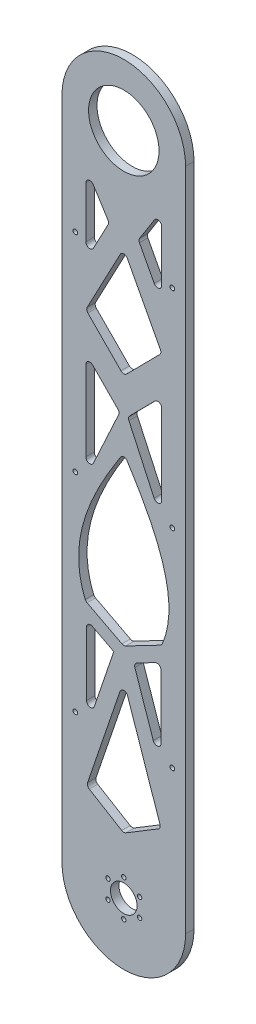
SolidWorks part; units mm, degrees
material "1060 Alloy"
ref_plane "Front Plane" through (0, 0, 0) normal (0, 0, 1) x (1, 0, 0)
ref_plane "Top Plane" through (0, 0, 0) normal (0, 1, 0) x (1, 0, 0)
ref_plane "Right Plane" through (0, 0, 0) normal (1, 0, 0) x (0, 0, -1)
sketch "Sketch2" plane through (0, 0, 0) normal (0, 0, 1) x (1, 0, 0)
  line L0 (0, 0) -> (0, 500) construction
  line L1 (-46.5, 0) -> (-46.5, 500)
  line L2 (46.5, 0) -> (46.5, 500)
  arc A0 (-46.5, 0) -> (46.5, 0) centre (0, 0) ccw
  arc A1 (46.5, 500) -> (-46.5, 500) centre (0, 500) ccw
  circle A2 centre (0, 500) radius 37.25 construction
  circle A3 centre (0, 0) radius 10
  circle A4 centre (0, 13.75) radius 1.65
  circle A5 centre (0, 0) radius 13.75 construction
  circle A6 centre (11.9078, 6.875) radius 1.65
  circle A7 centre (11.9078, -6.875) radius 1.65
  circle A8 centre (0, -13.75) radius 1.65
  circle A9 centre (-11.9078, -6.875) radius 1.65
  circle A10 centre (-11.9078, 6.875) radius 1.65
  point P3 (0, 250)
  point P27 (0, 0)
  dimension "D2" = 74.5
  dimension "D4" = 20
  dimension "D5" = 3.3
  dimension "D6" = 27.5
  dimension "D3" = 46.5
  dimension "D1" = 500
  dimension "D7" = 6
extrude "Boss-Extrude1" add sketch "Sketch2" along normal blind 6.35
sketch "Sketch4" plane through (0, 0, 6.35) normal (0, 0, 1) x (1, 0, 0)
  line L0 (0, 500) -> (0, 999.1647) construction
  line L29 (46.5, 500) -> (-46.5, 500) construction
  line L31 (28.0053, 59.376) -> (0, 42.4117)
  line L32 (0, 141.6934) -> (28.0053, 59.376)
  line L33 (-28.0053, 59.376) -> (0, 141.6934)
  line L34 (0, 42.4117) -> (-28.0053, 59.376)
  line L35 (-7.5, 156.9059) -> (-28.0053, 96.6336)
  line L36 (-28.0053, 167.5829) -> (-7.5, 156.9059)
  line L37 (-28.0053, 96.6336) -> (-28.0053, 167.5829)
  line L38 (28.0053, 167.5829) -> (7.5, 156.9059)
  line L39 (28.0053, 96.6336) -> (28.0053, 167.5829)
  line L40 (7.5, 156.9059) -> (28.0053, 96.6336)
  line L41 (0, 164.2751) -> (28.5505, 179.1412)
  line L42 (0, 164.2751) -> (-28.5505, 179.1412)
  line L43 (28.5505, 259.5868) -> (3, 314.9383)
  line L44 (28.5505, 340.7931) -> (28.5505, 259.5868)
  line L45 (3, 314.9383) -> (28.5505, 340.7931)
  line L46 (-3, 314.9383) -> (-28.5505, 340.7931)
  line L47 (-28.5505, 259.5868) -> (-3, 314.9383)
  line L48 (-28.5505, 340.7931) -> (-28.5505, 259.5868)
  line L49 (0, 423.1428) -> (-28.5505, 369.2462)
  line L50 (-28.5505, 369.2462) -> (0, 340.3557)
  line L51 (0, 340.3557) -> (28.5505, 369.2462)
  line L52 (0, 423.1428) -> (28.5505, 369.2462)
  line L53 (-28.5505, 462.0952) -> (-28.5505, 401.2902)
  line L54 (-11, 434.4215) -> (-28.5505, 462.0952)
  line L55 (-28.5505, 401.2902) -> (-11, 434.4215)
  line L56 (28.5505, 401.2902) -> (11, 434.4215)
  line L57 (28.5505, 462.0952) -> (28.5505, 401.2902)
  line L58 (11, 434.4215) -> (28.5505, 462.0952)
  arc A0 (46.5, 500) -> (-46.5, 500) centre (0, 500) ccw construction
  arc A1 (46.5, 500) -> (-46.5, 500) centre (0, 500) ccw construction
  spline S2 degree 3 poles (28.5505, 179.1412) (45.3203, 216.9857) (19.4301, 259.7903) (0, 290.0258) knots 0 0 0 0 1 1 1 1
  spline S3 degree 3 poles (-28.5505, 179.1412) (-45.3203, 216.9857) (-19.4301, 259.7903) (0, 290.0258) knots 0 0 0 0 1 1 1 1
extrude "Cut-Extrude1" cut sketch "Sketch4" against normal blind 10
fillet "Fillet3" radius 3 29 edges at (-11, 434.4215, 3.175) (-28.5505, 401.2902, 3.175) (28.5505, 401.2902, 3.175) (11, 434.4215, 3.175) (28.5505, 462.0952, 3.175) (-28.5505, 462.0952, 3.175) (0, 423.1428, 3.175) (-28.5505, 369.2462, 3.175) (28.5505, 369.2462, 3.175) (0, 340.3557, 3.175) (28.5505, 340.7931, 3.175) (-28.5505, 340.7931, 3.175) (-3, 314.9383, 3.175) (3, 314.9383, 3.175) (28.5505, 259.5868, 3.175) (-28.5505, 259.5868, 3.175) (28.5505, 179.1412, 3.175) (0, 290.0258, 3.175) (-28.5505, 179.1412, 3.175) (0, 164.2751, 3.175) (-28.0053, 96.6336, 3.175) (28.0053, 96.6336, 3.175) (7.5, 156.9059, 3.175) (-28.0053, 167.5829, 3.175) (28.0053, 167.5829, 3.175) (0, 141.6934, 3.175) (28.0053, 59.376, 3.175) (-28.0053, 59.376, 3.175) (0, 42.4117, 3.175)
sketch "Sketch5" plane through (0, 0, 6.35) normal (0, 0, 1) x (1, 0, 0)
  line L0 (0, -46.5) -> (108.8395, -46.5) construction
  line L1 (46.5, 100) -> (-46.5, 100) construction
  line L2 (46.5, 0) -> (46.5, 500) construction
  line L3 (-46.5, 500) -> (-46.5, 0) construction
  line L4 (-46.5, 106.35) -> (46.5, 106.35) construction
  line L5 (36.5, 106.35) -> (36.5, 100) construction
  line L6 (0, 106.35) -> (0, 100) construction
  line L7 (-46.5, 256.35) -> (46.5, 256.35) construction
  line L8 (-46.5, 181.35) -> (46.5, 181.35) construction
  line L9 (-46.5, 337.7) -> (46.5, 337.7) construction
  arc A1 (-46.5, 0) -> (46.5, 0) centre (0, 0) ccw construction
  circle A2 centre (36.5, 103.175) radius 1.75
  circle A3 centre (-36.5, 103.175) radius 1.75
  circle A4 centre (36.5, 259.525) radius 1.75
  circle A5 centre (-36.5, 259.525) radius 1.75
  circle A6 centre (36.5, 415.875) radius 1.75
  circle A7 centre (-36.5, 415.875) radius 1.75
  point P18 (36.5, 103.175)
  dimension "D2" = 3.5
  dimension "D1" = 146.5
  dimension "D3" = 10
  dimension "D4" = 6.35
  dimension "D5" = 150
  dimension "D6" = 81.35
  dimension "D7" = 81.35
extrude "Cut-Extrude2" cut sketch "Sketch5" against normal through all
sketch "Sketch6" plane through (0, 0, 6.35) normal (0, 0, 1) x (1, 0, 0)
  circle A0 centre (0, 500) radius 26.5
  arc A1 (46.5, 500) -> (-46.5, 500) centre (0, 500) ccw construction
  arc A2 (46.5, 500) -> (-46.5, 500) centre (0, 500) ccw construction
  point P5 (0, 0)
  dimension "D1" = 20
extrude "Cut-Extrude3" cut sketch "Sketch6" against normal blind 10
equation "\"L1L\"=500"
equation "\"L1Thick\"=6.35"
equation "\"D1@Sketch2\"=\"L1L\""
equation "\"Harm-Drive-Outer\"=74.5"
equation "\"D2@Sketch2\"=\"Harm-Drive-Outer\""
equation "\"D1@Boss-Extrude1\"=\"L1Thick\""
